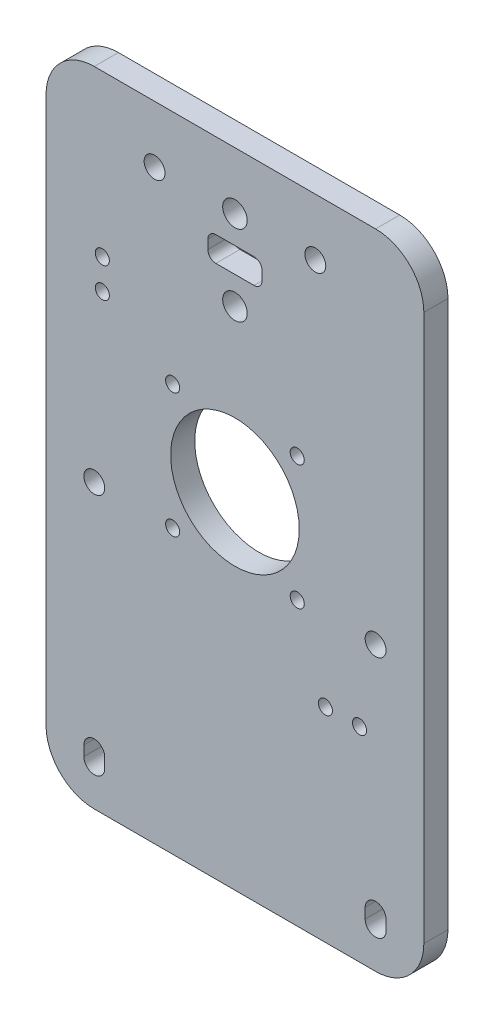
SolidWorks part; units mm, degrees
material "Polycarbonate (PC)"
ref_plane "Спереди" through (0, 0, 0) normal (0, 0, 1) x (1, 0, 0)
ref_plane "Сверху" through (0, 0, 0) normal (0, 1, 0) x (1, 0, 0)
ref_plane "Справа" through (0, 0, 0) normal (1, 0, 0) x (0, 0, -1)
sketch "Model" plane through (0, 0, 0) normal (0, 0, 1) x (1, 0, 0)
  line L0 (-2.3021, 85.8) -> (5.2264, 85.8) construction
  line L1 (6.75, 135.8) -> (-6.75, 135.8) construction
  line L5 (0, 27.6115) -> (0, 0) construction
  line L24 (-35, 64.9169) -> (-35, 77.3985) construction
  line L25 (-31.4983, 12.5) -> (-38.4, 12.5) construction
  line L26 (-31.4983, 10) -> (-38.4, 10) construction
  line L27 (-35, 12.5) -> (-35, 10) construction
  line L28 (-32.4, 12.5) -> (-32.4, 10)
  line L29 (-37.6, 12.5) -> (-37.6, 10)
  line L40 (31.4983, 10) -> (38.4, 10) construction
  line L41 (31.4983, 12.5) -> (38.4, 12.5) construction
  line L42 (35, 64.9169) -> (35, 77.3985) construction
  line L43 (35, 12.5) -> (35, 10) construction
  line L44 (32.4, 12.5) -> (32.4, 10)
  line L45 (37.6, 12.5) -> (37.6, 10)
  line L47 (-26.0102, 145.8) -> (26.0946, 145.8) construction
  line L48 (0, 129.408) -> (0, 90.7064) construction
  line L51 (-38.85, 70.45) -> (-29.8907, 70.45) construction
  line L53 (-16.3166, 125.8) -> (17.7871, 125.8) construction
  line L58 (38.85, 70.45) -> (29.8907, 70.45) construction
  line L4875 (-35, 160) -> (35, 160)
  line L4882 (47, 148) -> (47, 12)
  line L4889 (35, 0) -> (-35, 0)
  line L4896 (-47, 12) -> (-47, 148)
  line L5609 (6.75, 138.9) -> (-6.75, 138.9)
  line L5610 (-6.75, 138.9) -> (-6.75, 132.7)
  line L5611 (-6.75, 132.7) -> (6.75, 132.7)
  line L5612 (6.75, 132.7) -> (6.75, 138.9)
  line L6648 (-6.75, 138.9) -> (6.75, 138.9)
  line L6649 (6.75, 138.9) -> (6.75, 132.7)
  line L6650 (6.75, 132.7) -> (-6.75, 132.7)
  line L6651 (-6.75, 132.7) -> (-6.75, 138.9)
  arc A0 (-47, 12) -> (-35, 0) centre (-35, 12) ccw
  arc A1 (35, 0) -> (47, 12) centre (35, 12) ccw
  arc A2 (47, 148) -> (35, 160) centre (35, 148) ccw
  arc A3 (-35, 160) -> (-47, 148) centre (-35, 148) ccw
  circle A4 centre (0, 85.8) radius 16
  arc A13 (-32.4, 12.5) -> (-37.6, 12.5) centre (-35, 12.5) ccw
  arc A14 (-37.6, 10) -> (-32.4, 10) centre (-35, 10) ccw
  arc A19 (32.4, 12.5) -> (37.6, 12.5) centre (35, 12.5) cw
  arc A20 (37.6, 10) -> (32.4, 10) centre (35, 10) cw
  circle A29 centre (0, 145.8) radius 3.05
  circle A30 centre (-20, 145.8) radius 2.6
  circle A31 centre (20, 145.8) radius 2.6
  circle A32 centre (-35, 70.45) radius 2.6
  circle A33 centre (0, 125.8) radius 3.05
  circle A36 centre (35, 70.45) radius 2.6
  point P17 (0, 0)
  point P77 (-35, 11.25)
  point P114 (35, 11.25)
  point P127 (0, 160)
  dimension "D5" = 32
  dimension "D8" = 94
  dimension "D30" = 5.2
  dimension "D33" = 5.2
  dimension "D35" = 6.1
  dimension "D14" = 12
  dimension "D3" = 160
  dimension "D6" = 60.45
  dimension "D7" = 74.2
  dimension "D9" = 70
  dimension "D10" = 24.2
  dimension "D12" = 20
  dimension "D13" = 20
  dimension "D16" = 2.5
  dimension "D17" = 10
  dimension "D18" = 5.2
  dimension "D25" = 14.2
  dimension "D34" = 20
  dimension "D41" = 13.5
  dimension "D42" = 6.2
extrude "Base" add sketch "Model" along normal blind 6 contours L4875 A3 L4896 A0 L4889 A1 L4882 A2 L45 A20 L44 A19 region at (0, 158.1443, 0)
fillet "FilletCableSlot" radius 2 4 edges at (6.75, 138.9, 3) (-6.75, 138.9, 3) (-6.75, 132.7, 3) (6.75, 132.7, 3)
hole_wizard "Ø3.2 (3.2) Stepper mount Holes" positions "Sketch6" profile "Sketch7" hole size "Ø3.5" standard "ANSI Metric" end condition through all
sketch "Sketch6" plane through (0, 0, 6) normal (0, 0, 1) x (1, 0, 0)
  line L2 (0, 0) -> (0, 95.4376) construction
  line L3 (35, 0) -> (-35, 0) construction
  point P0 (-15.5, 101.3)
  point P3 (-15.5, 70.3)
  point P6 (15.5, 70.3)
  point P9 (15.5, 101.3)
  dimension "D1" = 31
  dimension "D2" = 31
  dimension "D3" = 70.3
sketch "Sketch7" plane through (-15.5, 101.3, 6) normal (1, 0, 0) x (0, -1, 0)
  line L0 (0, 0) -> (0, 6)
  line L1 (0, 6) -> (1.75, 6)
  line L2 (1.75, 6) -> (1.75, 0)
  line L5 (1.75, 0) -> (0, 0)
  line L11 (0, -6.35) -> (0, 107.95) construction
  dimension "Thru Hole Dia." = 3.5
  dimension "Thru Hole Depth" = 6
hole_wizard "Ø3.5 (3.5) SensorMount" positions "Sketch8" profile "Sketch9" hole size "Ø3.5" standard "ANSI Metric" end condition through all
sketch "Sketch8" plane through (0, 0, 6) normal (0, 0, 1) x (1, 0, 0)
  line L0 (-35, 160) -> (35, 160) construction
  line L1 (-47, 12) -> (-47, 148) construction
  point P0 (-33, 120)
  point P2 (-33, 112.5)
  dimension "D1" = 7.5
  dimension "D2" = 40
  dimension "D3" = 14
sketch "Sketch9" plane through (-33, 120, 6) normal (1, 0, 0) x (0, -1, 0)
  line L0 (0, 0) -> (0, 6)
  line L1 (0, 6) -> (1.75, 6)
  line L2 (1.75, 6) -> (1.75, 0)
  line L5 (1.75, 0) -> (0, 0)
  line L11 (0, -6.35) -> (0, 107.95) construction
  dimension "Thru Hole Dia." = 3.5
  dimension "Thru Hole Depth" = 6
hole_wizard "Ø3.5 (3.5) CableMount" positions "Sketch10" profile "Sketch11" hole size "Ø3.5" standard "ANSI Metric" end condition through all
sketch "Sketch10" plane through (0, 0, 6) normal (0, 0, 1) x (1, 0, 0)
  line L0 (35, 0) -> (-35, 0) construction
  line L1 (47, 148) -> (47, 12) construction
  point P0 (22.5, 50.76)
  point P2 (31, 50.76)
  dimension "D1" = 8.5
  dimension "D2" = 50.76
  dimension "D3" = 16
sketch "Sketch11" plane through (22.5, 50.76, 6) normal (1, 0, 0) x (0, -1, 0)
  line L0 (0, 0) -> (0, 6)
  line L1 (0, 6) -> (1.75, 6)
  line L2 (1.75, 6) -> (1.75, 0)
  line L5 (1.75, 0) -> (0, 0)
  line L11 (0, -6.35) -> (0, 107.95) construction
  dimension "Thru Hole Dia." = 3.5
  dimension "Thru Hole Depth" = 6
